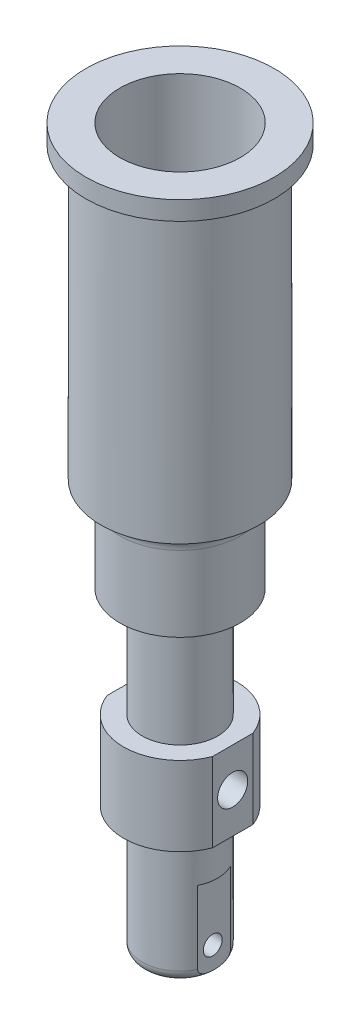
SolidWorks part; units mm, degrees
ref_plane "Спереди" through (0, 0, 0) normal (0, 0, 1) x (1, 0, 0)
ref_plane "Сверху" through (0, 0, 0) normal (0, 1, 0) x (1, 0, 0)
ref_plane "Справа" through (0, 0, 0) normal (1, 0, 0) x (0, 0, -1)
sketch "Эскиз1" plane through (0, 0, 0) normal (0, 1, 0) x (1, 0, 0)
  circle A0 centre (0, 0) radius 16
  circle A1 centre (0, 0) radius 21
  dimension "D1" = 32
  dimension "D2" = 42
extrude "Вытянуть1" add sketch "Эскиз1" along normal blind 70
sketch "Эскиз3" plane through (0, 0, 0) normal (0, -1, 0) x (1, 0, 0)
  circle A0 centre (0, 0) radius 21
  dimension "D1" = 42
extrude "Вытянуть2" add sketch "Эскиз3" along normal blind 7
sketch "Эскиз4" plane through (0, -7, 0) normal (0, -1, 0) x (1, 0, 0)
  circle A0 centre (0, 0) radius 10
  dimension "D1" = 20
extrude "Вытянуть3" add sketch "Эскиз4" along normal blind 109
fillet "Скругление4" radius 3 1 edges at (0, -116, -10)
sketch "Эскиз5" plane through (0, 0, 0) normal (0, 0, 1) x (1, 0, 0)
  line L0 (0, -110.8116) -> (0, -125.3162) construction
  line L1 (-16.8478, -93.6617) -> (-9.0144, -93.6617)
  line L3 (-9.0144, -93.6617) -> (-9.0144, -122.6685)
  line L4 (-16.8478, -93.6617) -> (-16.8478, -122.6685)
  line L5 (-16.8478, -122.6685) -> (-9.0144, -122.6685)
  line L6 (16.8478, -122.6685) -> (9.0144, -122.6685)
  line L7 (16.8478, -93.6617) -> (16.8478, -122.6685)
  line L8 (9.0144, -93.6617) -> (9.0144, -122.6685)
  line L9 (16.8478, -93.6617) -> (9.0144, -93.6617)
extrude "Вырез-Вытянуть1" cut sketch "Эскиз5" against normal mid plane 76
sketch "Эскиз9" plane through (-27.0166, 0, -1.0236) normal (-0.9993, 0, -0.0379) x (-0.0379, 0, 0.9993)
  circle A0 centre (0, -109.3588) radius 2.5
extrude "Вырез-Вытянуть3" cut sketch "Эскиз9" against normal mid plane 155
sketch "Эскиз10" plane through (0, -7, 0) normal (0, -1, 0) x (1, 0, 0)
  circle A0 centre (0, 0) radius 16
extrude "Вытянуть4" add sketch "Эскиз10" along normal blind 25
fillet "Скругление5" radius 5 1 edges at (0, -7, -16)
sketch "Эскиз11" plane through (0, 70, 0) normal (0, 1, 0) x (1, 0, 0)
  circle A0 centre (0, 0) radius 16
  circle A1 centre (0, 0) radius 25
extrude "Вытянуть5" add sketch "Эскиз11" along normal blind 5
ref_plane "Плоскость1" through (0, -61, 0) normal (0, -1, 0) x (1, 0, 0)
sketch "Эскиз14" plane through (0, -61, 0) normal (0, -1, 0) x (1, 0, 0)
  circle A0 centre (0, 0) radius 15
extrude "Вытянуть6" add sketch "Эскиз14" along normal blind 21
sketch "Эскиз7" plane through (-26.476, 0, -1.0031) normal (-0.9993, 0, -0.0379) x (-0.0379, 0, 0.9993)
  circle A0 centre (-0.4881, -71.2987) radius 4
extrude "Вырез-Вытянуть2" cut sketch "Эскиз7" against normal mid plane 155
sketch "Эскиз15" plane through (0, 0, 0) normal (0, 0, 1) x (1, 0, 0)
  line L0 (0, -81.9686) -> (0, -45.5729) construction
  line L1 (-23.4611, -55.1125) -> (-14.0112, -55.1125)
  line L2 (-23.4611, -55.1125) -> (-23.4611, -87.1808)
  line L3 (-23.4611, -87.1808) -> (-14.0112, -87.1808)
  line L4 (-14.0112, -55.1125) -> (-14.0112, -87.1808)
  line L5 (23.4611, -87.1808) -> (14.0112, -87.1808)
  line L6 (23.4611, -55.1125) -> (23.4611, -87.1808)
  line L7 (14.0112, -55.1125) -> (14.0112, -87.1808)
  line L8 (23.4611, -55.1125) -> (14.0112, -55.1125)
extrude "Вырез-Вытянуть4" cut sketch "Эскиз15" against normal mid plane 51
